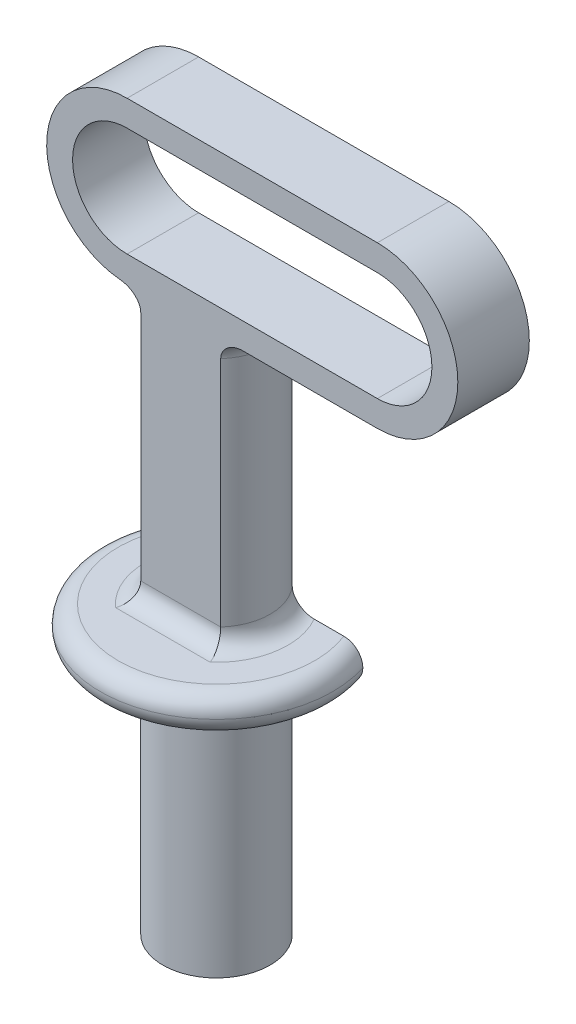
SolidWorks part; units mm, degrees
ref_plane "前视基准面" through (0, 0, 0) normal (0, 0, 1) x (1, 0, 0)
ref_plane "上视基准面" through (0, 0, 0) normal (0, 1, 0) x (1, 0, 0)
ref_plane "右视基准面" through (0, 0, 0) normal (1, 0, 0) x (0, 0, -1)
other "Configuration Table"
sketch "草图1" plane through (0, 0, 0) normal (0, 0, 1) x (1, 0, 0)
  line L0 (0, 4.5) -> (14, 4.5)
  line L1 (14, -4.5) -> (0, -4.5)
  arc A0 (0, 4.5) -> (0, -4.5) centre (0, 0) ccw
  arc A1 (14, -4.5) -> (14, 4.5) centre (14, 0) ccw
  dimension "D1" = 9
  dimension "D2" = 14
extrude "凸台-拉伸1" add sketch "草图1" along normal blind 4
sketch "草图3" plane through (0, 0, 0) normal (0, 0, -1) x (-1, 0, 0)
  line L0 (-14, 3.05) -> (0, 3.05)
  line L1 (0, -3.05) -> (-14, -3.05)
  arc A0 (0, -3.05) -> (0, 3.05) centre (0, 0) ccw
  arc A1 (-14, 3.05) -> (-14, -3.05) centre (-14, 0) ccw
  dimension "D1" = 6.1
extrude "切除-拉伸1" cut sketch "草图3" against normal through all
sketch "草图4" plane through (0, -4.5, 0) normal (0, -1, 0) x (1, 0, 0)
  line L0 (0, 4) -> (14, 4) construction
  line L1 (0.7639, 0) -> (5.2361, 0)
  line L2 (0, 0) -> (14, 0) construction
  line L3 (0, 4) -> (0, 0) construction
  line L4 (0.7639, 4) -> (5.2361, 4)
  line L5 (14, 4) -> (14, 0) construction
  arc A0 (0.7639, 4) -> (0.7639, 0) centre (3, 2) ccw
  arc A1 (5.2361, 0) -> (5.2361, 4) centre (3, 2) ccw
  point P2 (5.2361, 0)
  point P8 (0, 2)
  point P9 (0.7639, 4)
  point P12 (5.2361, 4)
  point P13 (0.7639, 0)
  dimension "D1" = 6
  dimension "D2" = 11
extrude "凸台-拉伸2" add sketch "草图4" along normal blind 15
sketch "草图5" plane through (0, -19.5, 0) normal (0, -1, 0) x (1, 0, 0)
  line L4 (-3.1847, 0) -> (9.1847, 0)
  line L5 (0.7639, 0) -> (5.2361, 0) construction
  arc A3 (9.1847, 0) -> (-3.1847, 0) centre (3, 2) ccw
  dimension "D1" = 13
extrude "凸台-拉伸3" add sketch "草图5" along normal blind 2
sketch "草图6" plane through (0, -21.5, 0) normal (0, -1, 0) x (1, 0, 0)
  line L4 (0.7639, 0) -> (5.2361, 0)
  line L5 (-3.1847, 0) -> (9.1847, 0) construction
  arc A3 (5.2361, 0) -> (0.7639, 0) centre (3, 2) ccw
  arc A4 (9.1847, 0) -> (-3.1847, 0) centre (3, 2) ccw construction
  dimension "D1" = 6
extrude "凸台-拉伸4" add sketch "草图6" along normal blind 14
sketch "草图7" plane through (0, -35.5, 0) normal (0, -1, 0) x (1, 0, 0)
  circle A2 centre (3, 2) radius 1.25
  arc A3 (5.2361, 0) -> (0.7639, 0) centre (3, 2) ccw construction
  dimension "D1" = 2.5
extrude "切除-拉伸2" cut sketch "草图7" against normal blind 3.5
fillet "圆角1" radius 1 3 edges at (6, -19.5, 2) (3, -19.5, 4) (0, -19.5, 2)
fillet "圆角2" radius 1 3 edges at (6, -4.5, 2) (0.1975, -4.5, 3.0705) (0.1975, -4.5, 0.9295)
chamfer "倒角1" distance 0.5 angle 45 1 edges at (4.25, -35.5, 2)
fillet "圆角3" radius 1 2 edges at (3, -19.5, 8.5) (3, -21.5, 8.5)
